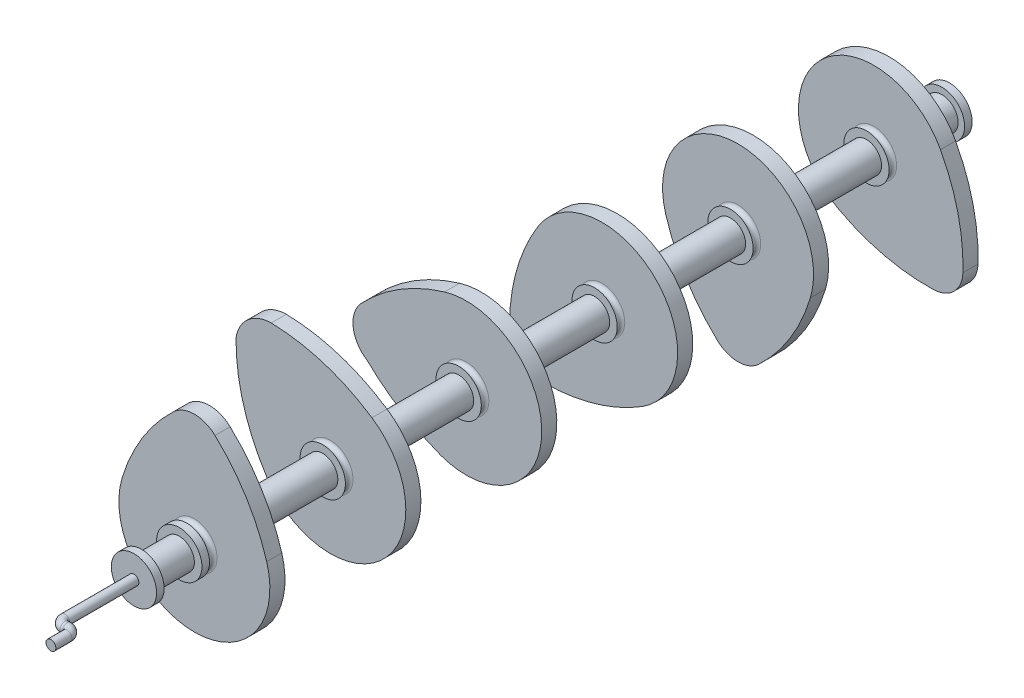
SolidWorks part; units mm, degrees
ref_plane "Front Plane" through (0, 0, 0) normal (0, 0, 1) x (1, 0, 0)
ref_plane "Top Plane" through (0, 0, 0) normal (0, 1, 0) x (1, 0, 0)
ref_plane "Right Plane" through (0, 0, 0) normal (1, 0, 0) x (0, 0, -1)
sketch "Sketch1" plane through (0, 0, 0) normal (0, 0, 1) x (1, 0, 0)
  circle A0 centre (0, 0) radius 76.2
  dimension "D1" = 152.4
extrude "Boss-Extrude4" add sketch "Sketch1" along normal blind 25.4
sketch "Sketch7" plane through (0, 0, 25.4) normal (0, 0, 1) x (1, 0, 0)
  circle A0 centre (0, 0) radius 50.8
  dimension "D1" = 101.6
extrude "Boss-Extrude5" add sketch "Sketch7" along normal blind 127
sketch "Sketch8" plane through (0, 0, 152.4) normal (0, 0, 1) x (1, 0, 0)
  circle A0 centre (0, 0) radius 76.2
extrude "Boss-Extrude6" add sketch "Sketch8" along normal blind 25.4
sketch "Sketch10" plane through (0, 0, 0) normal (1, 0, 0) x (0, 0, -1)
  line L1 (0, 0) -> (25.4, 0)
  line L2 (0, 0) -> (0, 76.2)
  line L4 (25.4, 0) -> (25.4, 76.2)
  arc A0 (0, 76.2) -> (25.4, 76.2) centre (12.7, 76.2) ccw
  dimension "D1" = 25.4
revolve "Revolve2" add sketch "Sketch10" angle 360 about L1
sketch "Sketch11" plane through (0, 0, -25.4) normal (0, 0, -1) x (-1, 0, 0)
  line L0 (0, 689.2095) -> (0, 381) construction
  line L1 (0, -254) -> (0, -398.6698) construction
  arc A6 (-243.2474, 73.1212) -> (243.2474, 73.1212) centre (0, 0) ccw
  arc A8 (-69.4993, 353.5108) -> (-243.2474, 73.1212) centre (364.8711, -109.6818) ccw
  arc A9 (69.4993, 353.5108) -> (243.2474, 73.1212) centre (-364.8711, -109.6818) cw
  arc A11 (69.4993, 353.5108) -> (-69.4993, 353.5108) centre (0, 279.4) ccw
  dimension "D4" = 279.4
  dimension "D2" = 508
  dimension "D5" = 1270
extrude "Boss-Extrude7" add sketch "Sketch11" along normal blind 50.8
sketch "Sketch12" plane through (0, 0, -76.2) normal (0, 0, -1) x (-1, 0, 0)
  circle A0 centre (0, 0) radius 50.8
  dimension "D1" = 101.6
extrude "Boss-Extrude8" add sketch "Sketch12" along normal blind 381
sketch "Sketch13" plane through (0, 0, 0) normal (1, 0, 0) x (0, 0, -1)
  line L0 (457.2, -50.8) -> (457.2, 50.8) construction
  line L1 (457.2, 0) -> (482.6, 0)
  line L2 (457.2, 0) -> (457.2, 76.2)
  line L4 (482.6, 0) -> (482.6, 76.2)
  arc A0 (457.2, 76.2) -> (482.6, 76.2) centre (469.9, 76.2) ccw
  dimension "D1" = 25.4
revolve "Revolve3" add sketch "Sketch13" angle 360 about L1
sketch "Sketch14" plane through (0, 0, -482.6) normal (0, 0, -1) x (-1, 0, 0)
  arc A7 (-140.0553, 211.8974) -> (211.8974, -140.0553) centre (0, 0) ccw
  arc A9 (211.8974, -140.0553) -> (317.1209, 216.5629) centre (-317.8461, 210.083) ccw
  arc A10 (-140.0553, 211.8974) -> (198.801, 318.6145) centre (212.5044, -316.2376) cw
  arc A11 (317.1209, 216.5629) -> (198.801, 318.6145) centre (197.5656, 197.5656) ccw
  dimension "D5" = 279.4
  dimension "D2" = 508
  dimension "D6" = 1270
extrude "Boss-Extrude10" add sketch "Sketch14" along normal blind 50.8
sketch "Sketch15" plane through (0, 0, -533.4) normal (0, 0, -1) x (-1, 0, 0)
  circle A0 centre (0, 0) radius 50.8
  dimension "D1" = 101.6
extrude "Boss-Extrude11" add sketch "Sketch15" along normal blind 381 contours A0
sketch "Sketch17" plane through (0, 0, 0) normal (1, 0, 0) x (0, 0, -1)
  line L0 (914.4, -50.8) -> (914.4, 50.8) construction
  line L1 (914.4, 0) -> (939.8, 0)
  line L2 (914.4, 0) -> (914.4, 76.2)
  line L4 (939.8, 0) -> (939.8, 76.2)
  arc A0 (914.4, 76.2) -> (939.8, 76.2) centre (927.1, 76.2) ccw
  dimension "D1" = 76.2
  dimension "D2" = 25.4
revolve "Revolve4" add sketch "Sketch17" angle 360 about L1
sketch "Sketch18" plane through (0, 0, -939.8) normal (0, 0, -1) x (-1, 0, 0)
  arc A8 (333.4172, -86.0506) -> (353.5108, 69.4993) centre (279.4, 0) ccw
  arc A9 (353.5108, 69.4993) -> (73.1212, 243.2474) centre (-109.6818, -364.8711) ccw
  arc A10 (333.4172, -86.0506) -> (114.093, -226.9335) centre (-112.1272, 366.4041) cw
  arc A11 (73.1212, 243.2474) -> (114.093, -226.9335) centre (0, 0) ccw
  dimension "D4" = 279.4
  dimension "D3" = 203.2
  dimension "D5" = 1270
extrude "Boss-Extrude12" add sketch "Sketch18" along normal blind 50.8
sketch "Sketch19" plane through (0, 0, -990.6) normal (0, 0, -1) x (-1, 0, 0)
  circle A0 centre (0, 0) radius 50.8
  dimension "D1" = 101.6
extrude "Boss-Extrude13" add sketch "Sketch19" along normal blind 381
sketch "Sketch21" plane through (0, 0, 0) normal (1, 0, 0) x (0, 0, -1)
  line L0 (1371.6, -50.8) -> (1371.6, 50.8) construction
  line L1 (1371.6, 0) -> (1397, 0)
  line L2 (1371.6, 0) -> (1371.6, 76.2)
  line L4 (1397, 0) -> (1397, 76.2)
  arc A0 (1371.6, 76.2) -> (1397, 76.2) centre (1384.3, 76.2) ccw
  dimension "D1" = 76.2
  dimension "D2" = 25.4
revolve "Revolve5" add sketch "Sketch21" angle 360 about L1
sketch "Sketch22" plane through (0, 0, -1397) normal (0, 0, -1) x (-1, 0, 0)
  arc A9 (196.7755, -311.4312) -> (311.4312, -196.7755) centre (197.5656, -197.5656) ccw
  arc A10 (-134.1212, -215.7023) -> (196.7755, -311.4312) centre (201.1818, 323.5535) ccw
  arc A11 (215.7023, 134.1212) -> (311.4312, -196.7755) centre (-323.5535, -201.1818) cw
  arc A14 (215.7023, 134.1212) -> (-134.1212, -215.7023) centre (0, 0) ccw
  dimension "D5" = 1270
  dimension "D4" = 279.4
extrude "Boss-Extrude14" add sketch "Sketch22" along normal blind 50.8
sketch "Sketch23" plane through (0, 0, -1447.8) normal (0, 0, -1) x (-1, 0, 0)
  circle A0 centre (0, 0) radius 50.8
  dimension "D1" = 101.6
extrude "Boss-Extrude15" add sketch "Sketch23" along normal blind 381
sketch "Sketch24" plane through (0, 0, 0) normal (1, 0, 0) x (0, 0, -1)
  line L0 (1828.8, -50.8) -> (1828.8, 50.8) construction
  line L1 (1828.8, 0) -> (1854.2, 0)
  line L2 (1828.8, 0) -> (1828.8, 76.2)
  line L4 (1854.2, 0) -> (1854.2, 76.2)
  arc A0 (1828.8, 76.2) -> (1854.2, 76.2) centre (1841.5, 76.2) ccw
  dimension "D1" = 25.4
  dimension "D2" = 76.2
revolve "Revolve6" add sketch "Sketch24" angle 360 about L1
sketch "Sketch25" plane through (0, 0, -1854.2) normal (0, 0, -1) x (-1, 0, 0)
  line L2 (0, -215.9) -> (0, -254) construction
  arc A7 (243.2474, -73.1212) -> (-243.2474, -73.1212) centre (0, 0) ccw
  arc A8 (-69.4993, -353.5108) -> (69.4993, -353.5108) centre (0, -279.4) ccw
  arc A9 (-243.2474, -73.1212) -> (-69.4993, -353.5108) centre (364.8711, 109.6818) ccw
  arc A10 (243.2474, -73.1212) -> (69.4993, -353.5108) centre (-364.8711, 109.6818) cw
  dimension "D2" = 279.4
  dimension "D4" = 1270
  dimension "D3" = 203.2
  dimension "D5" = 508
extrude "Boss-Extrude16" add sketch "Sketch25" along normal blind 50.8
sketch "Sketch26" plane through (0, 0, -1905) normal (0, 0, -1) x (-1, 0, 0)
  circle A0 centre (0, 0) radius 50.8
  dimension "D1" = 101.6
extrude "Boss-Extrude17" add sketch "Sketch26" along normal blind 381
sketch "Sketch27" plane through (0, 0, 0) normal (1, 0, 0) x (0, 0, -1)
  line L0 (2286, -50.8) -> (2286, 50.8) construction
  line L1 (2286, 0) -> (2311.4, 0)
  line L2 (2286, 0) -> (2286, 76.2)
  line L4 (2311.4, 0) -> (2311.4, 76.2)
  arc A0 (2286, 76.2) -> (2311.4, 76.2) centre (2298.7, 76.2) ccw
  dimension "D1" = 25.4
  dimension "D2" = 76.2
revolve "Revolve7" add sketch "Sketch27" angle 360 about L1
sketch "Sketch28" plane through (0, 0, -2311.4) normal (0, 0, -1) x (-1, 0, 0)
  line L3 (-0.8271, 0) -> (0, 0) construction
  arc A6 (120.2974, -223.7064) -> (-223.7064, 120.2974) centre (0, 0) ccw
  arc A8 (-299.1133, -200.8265) -> (-200.8265, -299.1133) centre (-197.5656, -197.5656) ccw
  arc A9 (-200.8265, -299.1133) -> (120.2974, -223.7064) centre (-180.4461, 335.5596) ccw
  arc A10 (-299.1133, -200.8265) -> (-223.7064, 120.2974) centre (335.5596, -180.4461) cw
  dimension "D1" = 508
  dimension "D5" = 279.4
  dimension "D4" = 203.2
  dimension "D6" = 1270
extrude "Boss-Extrude18" add sketch "Sketch28" along normal blind 50.8
sketch "Sketch29" plane through (0, 0, -2362.2) normal (0, 0, -1) x (-1, 0, 0)
  circle A0 centre (0, 0) radius 54.3445
extrude "Boss-Extrude19" add sketch "Sketch29" along normal blind 177.8
sketch "Sketch30" plane through (0, 0, -2540) normal (0, 0, -1) x (-1, 0, 0)
  circle A0 centre (0, 0) radius 76.2
  dimension "D1" = 152.4
extrude "Boss-Extrude20" add sketch "Sketch30" along normal blind 25.4
sketch3d "3DSketch3"
  line L0 (0, 0, 177.8) -> (0, 0, 410.21)
  line L1 (0, 0, 177.8) -> (0, 0, 152.4) construction
  line L2 (21.59, 0, 431.8) -> (29.21, 0, 431.8)
  line L3 (50.8, 0, 453.39) -> (50.8, 0, 508)
  line L4 (0, 0, 0) -> (0, 0, 1007.9339) construction
  arc A0 (29.21, 0, 431.8) -> (50.8, 0, 453.39) centre (29.21, 0, 453.39) ccw
  arc A1 (21.59, 0, 431.8) -> (0, 0, 410.21) centre (21.59, 0, 410.21) ccw
  point P8 (50.8, 0, 431.8)
  point P9 (29.21, -21.59, 453.39)
  point P12 (0, 0, 431.8)
  point P13 (21.59, -21.59, 410.21)
  dimension "D4" = 21.59
  dimension "D1" = 254
  dimension "D2" = 50.8
  dimension "D3" = 76.2
sketch "Sketch33" plane through (0, 0, 177.8) normal (0, 0, 1) x (1, 0, 0)
  circle A0 centre (0, 0) radius 16.51
  dimension "D1" = 33.02
sweep "Sweep1" add profiles "Sketch33" path "3DSketch3"
